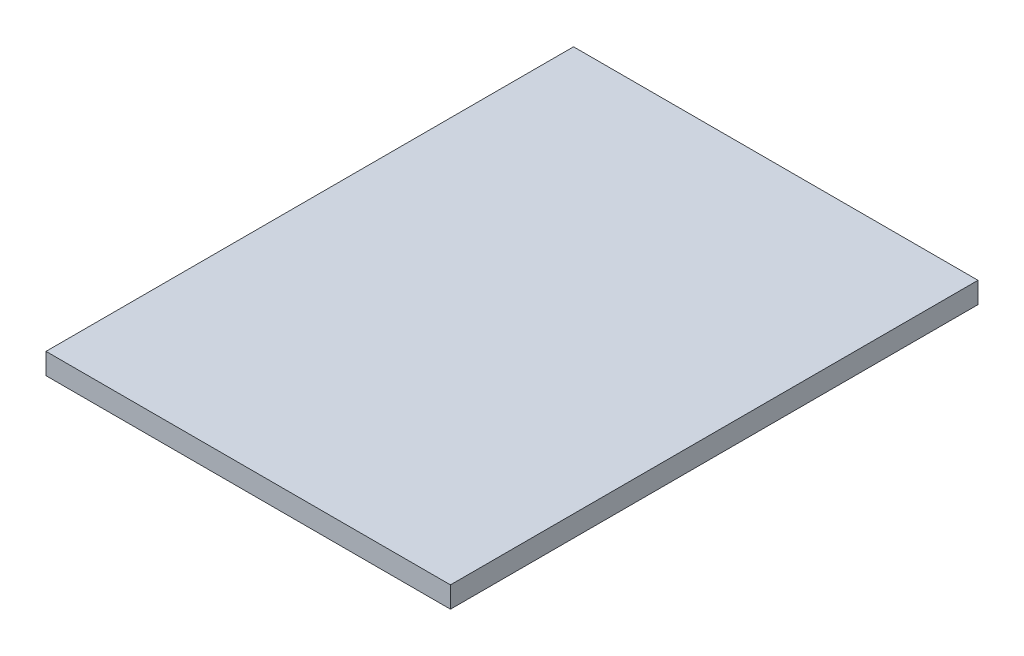
SolidWorks part; units mm, degrees
material "AISI 1020"
ref_plane "Спереди" through (0, 0, 0) normal (0, 0, 1) x (1, 0, 0)
ref_plane "Сверху" through (0, 0, 0) normal (0, 1, 0) x (1, 0, 0)
ref_plane "Справа" through (0, 0, 0) normal (1, 0, 0) x (0, 0, -1)
sketch "Эскиз1" plane through (0, 0, 0) normal (0, 1, 0) x (1, 0, 0)
  line L1 (-57.5, -75) -> (57.5, -75)
  line L2 (-57.5, -75) -> (-57.5, 75)
  line L3 (-57.5, 75) -> (57.5, 75)
  line L4 (57.5, -75) -> (57.5, 75)
  point P4 (0, 75)
  point P6 (57.5, 0)
  dimension "D1" = 150
  dimension "D2" = 115
base flange "Базовая кромка1" sketch "Эскиз1" thickness 6 reverse thickness direction no parameters "D1"=0.75
sketch "Сгиб-Линии1" plane through (0, 0, 0) normal (0, 1, 0) x (1, 0, 0)
sketch "Граничная рамка1" plane through (0, 0, 0) normal (0, 1, 0) x (1, 0, 0)
sheet metal parameters "Листовой металл3" thickness 6 parameters "D1"=0.75
flat pattern "Развертка3" [suppressed]
sketch "Сгиб-Линии2" plane through (0, 0, 0) normal (0, 1, 0) x (1, 0, 0)
sketch "Граничная рамка2" [suppressed] plane through (0, 0, 0) normal (0, 1, 0) x (1, 0, 0)
